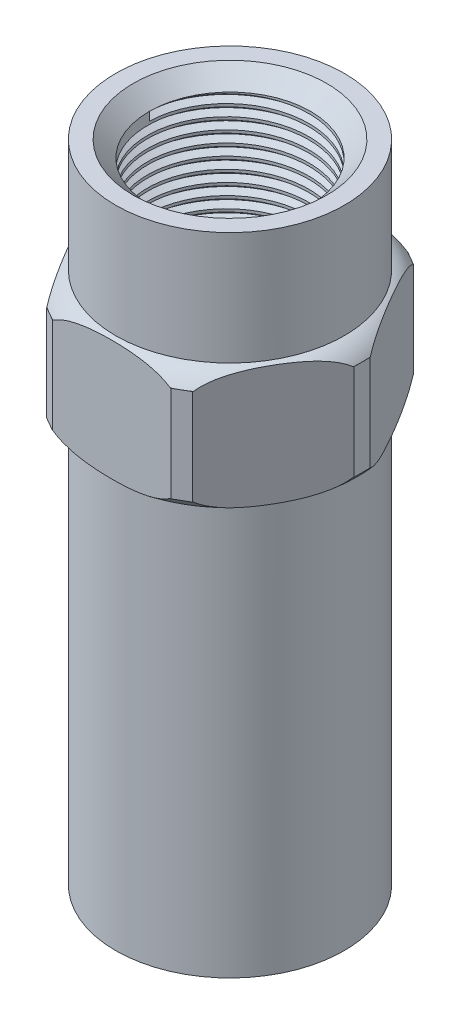
SolidWorks part; units mm, degrees
other "İşaretleme1"
sketch "Çizim17" plane through (13.0856, 30, 12.2767) normal (0.9808, 0.0611, 0.1854) x (0.0684, -0.9971, -0.0336)
material "AISI 304"
ref_plane "Ön Düzlem" through (0, 0, 0) normal (0, 0, 1) x (1, 0, 0)
ref_plane "Üst Düzlem" through (0, 0, 0) normal (0, 1, 0) x (1, 0, 0)
ref_plane "Sağ Düzlem" through (0, 0, 0) normal (1, 0, 0) x (0, 0, -1)
sketch "Çizim1" plane through (0, 0, 0) normal (0, 0, 1) x (1, 0, 0)
  line L0 (0, 66.0474) -> (0, -71.9763) construction
  line L1 (-118.1028, 0) -> (111.9368, 0) construction
  line L2 (-10.625, 19.5) -> (10.625, 8) construction
  line L3 (-10.625, -30) -> (10.625, -30)
  line L4 (-10.625, -30) -> (-10.625, 30)
  line L5 (-10.625, 30) -> (10.625, 30)
  line L6 (10.625, -30) -> (10.625, 30)
  line L7 (-10.625, -30) -> (10.625, 30) construction
  line L8 (-10.625, 30) -> (10.625, -30) construction
  line L9 (-10.625, 30) -> (10.625, 30)
  line L10 (-10.625, 30) -> (-10.625, 19.5)
  line L11 (-10.625, 19.5) -> (10.625, 19.5)
  line L12 (10.625, 30) -> (10.625, 19.5)
  line L13 (-10.625, 19.5) -> (10.625, 19.5)
  line L14 (-10.625, 19.5) -> (-10.625, 8)
  line L15 (-10.625, 8) -> (10.625, 8)
  line L16 (10.625, 19.5) -> (10.625, 8)
  line L17 (10.625, 19.5) -> (-10.625, 8) construction
  line L18 (0, 30) -> (0, -30)
  line L19 (11, 8) -> (-11, 8)
  line L20 (11, 8) -> (11, 19.5)
  line L21 (11, 19.5) -> (-11, 19.5)
  line L22 (-11, 8) -> (-11, 19.5)
  line L23 (11, 8) -> (-11, 19.5) construction
  line L24 (11, 19.5) -> (-11, 8) construction
  point P5 (0, 0)
  point P14 (0, 13.75)
  dimension "D1" = 60
  dimension "D2" = 21.25
  dimension "D3" = 10.5
  dimension "D4" = 11.5
  dimension "D5" = 22
revolve "Döndür1" add sketch "Çizim1" angle 360 about L18
sketch "Çizim2" plane through (0, 19.5, 0) normal (0, 1, 0) x (1, 0, 0)
  line L1 (-12.7017, 0) -> (-6.3509, -11)
  line L2 (-6.3509, -11) -> (6.3509, -11)
  line L3 (6.3509, -11) -> (12.7017, 0)
  line L4 (12.7017, 0) -> (6.3509, 11)
  line L5 (6.3509, 11) -> (-6.3509, 11)
  line L6 (-6.3509, 11) -> (-12.7017, 0)
  circle A0 centre (0, 0) radius 11
  circle A1 centre (0, 0) radius 11 construction
  circle M2 centre (0, 0) radius 11
extrude "Yükseklik-Ekstrüzyon1" add sketch "Çizim2" against normal blind 11.5 contours L6 L1 M2 | L5 L6 M2 | L4 L5 M2 | L3 L4 M2 | L2 L3 M2 | L1 L2 M2
chamfer "Pah1" distance 0.85 6 edges at (6.3509, 13.75, -11) (-6.3509, 13.75, -11) (-12.7017, 13.75, 0) (-6.3509, 13.75, 11) (6.3509, 13.75, 11) (12.7017, 13.75, 0)
sketch "Çizim3" plane through (0, 0, 0) normal (0, 0, 1) x (1, 0, 0)
  line L0 (-6.7759, 19.5) -> (-12.2767, 19.5) construction
  line L5 (-10.625, 30) -> (-10.625, 19.5) construction
  line L6 (-12.2767, 8) -> (-12.2767, 19.5) construction
  line L7 (-6.7759, 8) -> (-12.2767, 8) construction
  line L12 (0, 38.005) -> (0, -38.6416) construction
  line L13 (0, -12.1) -> (0, 12.1) construction
  line L14 (22.281, 0) -> (-20.4985, 0) construction
  line L15 (-10.625, 19.5) -> (-10.625, 19.7114)
  line L16 (-10.625, 19.7114) -> (-12.4699, 19.7114)
  line L17 (-12.4699, 19.7114) -> (-12.4699, 18.2114)
  line L18 (-12.4699, 18.2114) -> (-12.2767, 18.2114)
  line L19 (-12.2767, 9.3117) -> (-12.4699, 9.3117)
  line L20 (-12.4699, 9.3117) -> (-12.4699, 7.8117)
  line L21 (-12.4699, 7.8117) -> (-10.625, 7.8117)
  line L22 (-10.625, 8) -> (-10.625, -30) construction
  line L23 (-10.625, 7.8117) -> (-10.625, 8)
  spline S0 degree 2 poles (-10.625, 19.5) (-11.6733, 19.1184) (-12.2767, 18.2114) knots 0 0 0 1 1 1
  spline S1 degree 2 poles (-10.625, 8) (-11.6733, 8.3816) (-12.2767, 9.3117) knots 0 0 0 1 1 1
  dimension "D1" = 1.5
  dimension "D2" = 0.2114
  dimension "D3" = 0.1883
  dimension "D4" = 1.5
revolve "Kes-Döndür2" cut sketch "Çizim3" angle 360 about L12
sketch "Çizim4" plane through (0, -30, 0) normal (0, -1, 0) x (1, 0, 0)
  circle A0 centre (0, 0) radius 7.5
  dimension "D1" = 15
extrude "Kes-Ekstrüzyon1" cut sketch "Çizim4" against normal blind 15
sketch "Çizim6" plane through (0, -15, 0) normal (0, -1, 0) x (1, 0, 0)
  circle A0 centre (0, 0) radius 7.5
  circle A1 centre (0, 0) radius 4.7
  dimension "D1" = 2.8
extrude "Kes-Ekstrüzyon2" cut sketch "Çizim6" against normal blind 4 contours A1
sketch "Çizim7" plane through (0, 0, 0) normal (0, 0, 1) x (1, 0, 0)
  line L0 (-4.7, -15) -> (-7.5, -15)
  line L1 (-7.5, -15) -> (7.5, -15) construction
  line L2 (-4.7, -15) -> (4.7, -15) construction
  line L3 (-7.5, -15) -> (-4.7, -14)
  line L4 (-4.7, -14) -> (-4.7, -15)
  line L5 (0, -38.3067) -> (0, 37.4774)
  dimension "D1" = 1
revolve "Kes-Döndür3" cut sketch "Çizim7" angle 360 about L5
sketch "Çizim8" plane through (0, 30, 0) normal (0, 1, 0) x (1, 0, 0)
  circle A0 centre (0, 0) radius 7.5
  dimension "D1" = 15
extrude "Kes-Ekstrüzyon3" cut sketch "Çizim8" against normal blind 16 contours A0
sketch "Çizim16" plane through (0, 0, 0) normal (0, 0, 1) x (1, 0, 0)
  line L0 (-7.5, -30) -> (-7.5, -28.5)
  line L1 (-10.625, -30) -> (10.625, -30) construction
  line L2 (-7.5, -30) -> (7.5, -30) construction
  line L3 (-7.5, -28.5) -> (-9, -30)
  line L4 (-9, -30) -> (-7.5, -30)
  line L5 (-7.5, 30) -> (-9, 30)
  line L6 (7.5, 30) -> (-7.5, 30) construction
  line L7 (-9, 30) -> (-7.5, 28.5)
  line L8 (-7.5, 28.5) -> (-7.5, 30)
  line L9 (0, 40.5632) -> (0, -37.3227) construction
  dimension "D1" = 1.5
  dimension "D2" = 1.5
  dimension "D3" = 1.5
  dimension "D4" = 1.5
revolve "Kes-Döndür4" cut sketch "Çizim16" angle 360 about L9
thread "Diş1" pitch 1.0583 start angle 0, offset 0, length 13.75, pitch 1.0583, diameter 15
ref_plane "Düzlem1" through (-7.5, 28.5, 0) normal (0, 0, 1) x (-1, 0, 0)
sketch "Diş Profili1" plane through (-7.5, 28.5, 0) normal (0, 0, 1) x (-1, 0, 0)
  line L0 (0, 0) -> (0, 1.0583) construction
  line L1 (0, 0) -> (0.5728, 0.3307)
  line L2 (0.5728, 0.3307) -> (0.5728, 0.463)
  line L3 (0.5728, 0.463) -> (0, 0.7937)
  line L4 (0.5728, 0.3969) -> (0, 0.3969) construction
  line L11 (0, 0) -> (0, 0.7937)
  point P2 (0, 0)
  dimension "Pitch" = 1.0583
  dimension "Profile_Angle" = 60
  dimension "Profile_Land" = 0.1323
  dimension "Profile_Height" = 0.5728
thread "Diş2" pitch 1.0583 profile "Diş Profili2" start angle 0, offset 0, length 13, pitch 1.0583, diameter 15
ref_plane "Düzlem2" through (7.5, -28.5, 0) normal (0, 0, 1) x (1, 0, 0)
sketch "Diş Profili2" plane through (7.5, -28.5, 0) normal (0, 0, 1) x (1, 0, 0)
  line L0 (0, 0) -> (0, 1.0583) construction
  line L1 (0, 0) -> (0.5728, 0.3307)
  line L2 (0.5728, 0.3307) -> (0.5728, 0.463)
  line L3 (0.5728, 0.463) -> (0, 0.7937)
  line L4 (0.5728, 0.3969) -> (0, 0.3969) construction
  line L11 (0, 0) -> (0, 0.7937)
  point P2 (0, 0)
  dimension "Pitch" = 1.0583
  dimension "Profile_Angle" = 60
  dimension "Profile_Land" = 0.1323
  dimension "Profile_Height" = 0.5728
